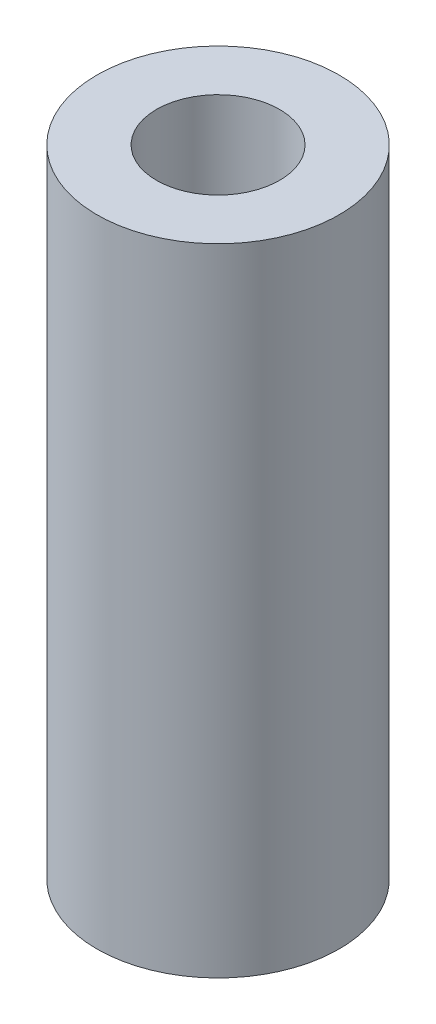
SolidWorks part; units mm, degrees
ref_plane "Front Plane" through (0, 0, 0) normal (0, 0, 1) x (1, 0, 0)
ref_plane "Top Plane" through (0, 0, 0) normal (0, 1, 0) x (1, 0, 0)
ref_plane "Right Plane" through (0, 0, 0) normal (1, 0, 0) x (0, 0, -1)
sketch "Sketch1" plane through (0, 0, 0) normal (0, 1, 0) x (1, 0, 0)
  circle A0 centre (0, 0) radius 6.35
  arc A4 (2.789, 5.7047) -> (-4.7997, -4.1576) centre (0, 0) ccw construction
  circle A5 centre (0, 0) radius 3.2258
  circle A6 centre (0, 0) radius 3.2258
  dimension "D1" = 0.0508
extrude "Boss-Extrude1" add sketch "Sketch1" along normal up to surface (33.3375 mm away)
